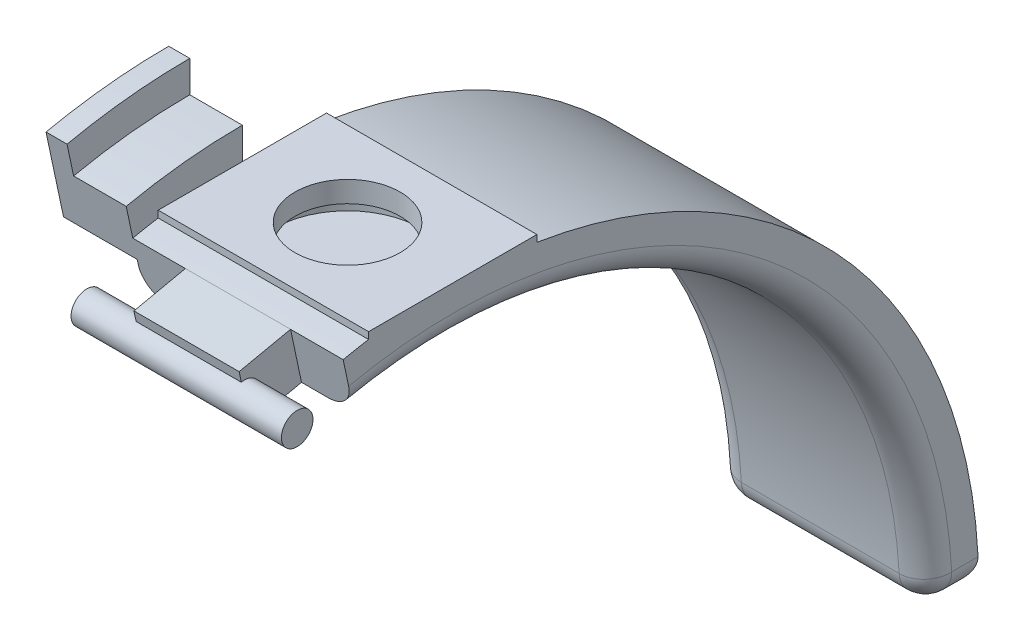
SolidWorks part; units mm, degrees
ref_plane "Front Plane" through (0, 0, 0) normal (0, 0, 1) x (1, 0, 0)
ref_plane "Top Plane" through (0, 0, 0) normal (0, 1, 0) x (1, 0, 0)
ref_plane "Right Plane" through (0, 0, 0) normal (1, 0, 0) x (0, 0, -1)
sketch "Sketch2" plane through (0, 0, 0) normal (1, 0, 0) x (0, 0, -1)
  line L0 (-50, 0) -> (-45, 0)
  line L1 (45, 0) -> (50, 0)
  arc A0 (45, 0) -> (-45, 0) centre (0, 0) ccw
  arc A1 (50, 0) -> (-50, 0) centre (0, 0) ccw
  dimension "D1" = 45
  dimension "D2" = 50
extrude "Boss-Extrude1" add sketch "Sketch2" along normal blind 20
sketch "Sketch3" plane through (0, 0, 0) normal (1, 0, 0) x (0, 0, -1)
  line L0 (0, 45) -> (8, 45)
  line L1 (8, 45) -> (8, 50)
  line L2 (8, 50) -> (-8, 50)
  line L3 (-8, 50) -> (-8, 45)
  line L4 (-8, 45) -> (0, 45)
  arc A0 (45, 0) -> (-45, 0) centre (0, 0) ccw construction
  dimension "D1" = 8
  dimension "D2" = 16
extrude "Boss-Extrude2" add sketch "Sketch3" along normal blind 20
sketch "Sketch4" plane through (0, 50, 0) normal (0, 1, 0) x (1, 0, 0)
  circle A0 centre (10, 0) radius 5
  dimension "D1" = 10
extrude "Cut-Extrude1" cut sketch "Sketch4" against normal blind 2
sketch "Sketch5" plane through (0, 48, 0) normal (0, 1, 0) x (1, 0, 0)
  circle A0 centre (10, 0) radius 7
  dimension "D1" = 14
extrude "Cut-Extrude2" cut sketch "Sketch5" against normal blind 2
sketch "Sketch9" plane through (0, 0, 0) normal (-1, 0, 0) x (0, 0, 1)
  line L0 (10, 46.9468) -> (11.0417, 51.8371)
  line L1 (0, 53) -> (0, 48)
  arc A0 (0, 48) -> (10, 46.9468) centre (0, 0) cw
  arc A1 (11.0417, 51.8371) -> (0, 53) centre (0, 0) ccw
  dimension "D2" = 48
  dimension "D1" = 10
  dimension "D3" = 5
extrude "Boss-Extrude5" add sketch "Sketch9" along normal blind 5
sketch "Sketch10" plane through (-5, 0, 0) normal (-1, 0, 0) x (0, 0, 1)
  line L0 (10, 46.9468) -> (10.4167, 48.9029) construction
  line L1 (10, 46.9468) -> (11.6667, 54.7712)
  line L2 (0, 56) -> (0, 48)
  arc A0 (0, 48) -> (10, 46.9468) centre (0, 0) cw
  arc A1 (11.6667, 54.7712) -> (0, 56) centre (0, 0) ccw
  dimension "D1" = 8
extrude "Boss-Extrude6" add sketch "Sketch10" along normal blind 2
sketch "Sketch11" plane through (0, 0, 0) normal (0, -1, 0) x (1, 0, 0)
  line L1 (0, 50) -> (20, 50)
  line L2 (0, 50) -> (0, 45)
  line L3 (0, 45) -> (20, 45)
  line L4 (20, 50) -> (20, 45)
sweep "Cut-Sweep2" cut profiles "Sketch11" path edge at (0, 31.4576, 38.8641)
sketch "Sketch12" plane through (0, 0, 0) normal (0, -0.2083, 0.9781) x (1, 0, 0)
  line L0 (20, 45) -> (0, 45) construction
  line L1 (10, 45) -> (5, 45)
  line L2 (10, 45) -> (10, 50)
  line L3 (10, 50) -> (5, 50)
  line L4 (5, 45) -> (5, 50)
  line L5 (0, 50) -> (20, 50) construction
  dimension "D1" = 5
extrude "Boss-Extrude7" add sketch "Sketch12" along normal blind 5
sketch "Sketch13" plane through (5, 0, 0) normal (-1, 0, 0) x (0, 0, 1)
  line L0 (15.307, 47.8612) -> (14.2653, 42.9709) construction
  circle A0 centre (14.7861, 45.4161) radius 1.5
  dimension "D1" = 3
extrude "Boss-Extrude8" add sketch "Sketch13" along normal blind 5 and the other way blind 5
mirror "Mirror1" about plane through (10, 42.9709, 14.2653) normal (-1, 0, 0) of "Boss-Extrude8", "Boss-Extrude7"
fillet "Fillet1" radius 2.5 6 edges at (10, 0, -45) (20, 0, -47.5) (10, 0, -50) (0, 0, -47.5) (0, 34.9777, -28.3119) (20, 34.9777, -28.3119)
